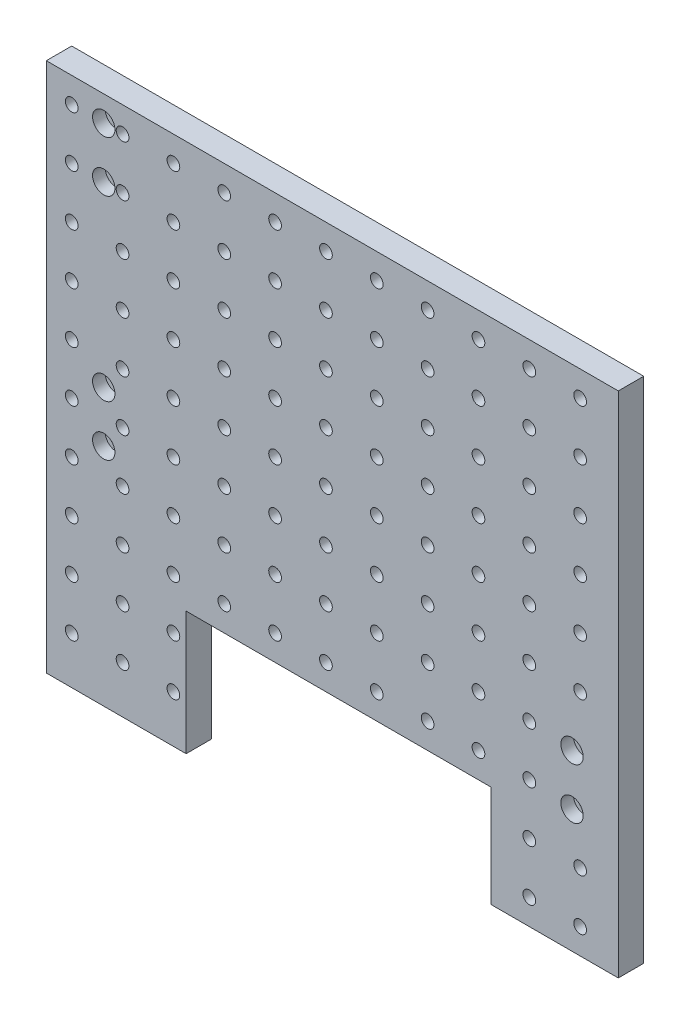
SolidWorks part; units mm, degrees
ref_plane "Front Plane" through (0, 0, 0) normal (0, 0, 1) x (1, 0, 0)
ref_plane "Top Plane" through (0, 0, 0) normal (0, 1, 0) x (1, 0, 0)
ref_plane "Right Plane" through (0, 0, 0) normal (1, 0, 0) x (0, 0, -1)
sketch "Sketch1" plane through (0, 0, 0) normal (0, 0, 1) x (1, 0, 0)
  line L1 (69.85, 0) -> (222.25, 0)
  line L2 (0, 0) -> (0, 203.2)
  line L3 (0, 203.2) -> (285.75, 203.2)
  line L4 (285.75, 0) -> (285.75, 203.2)
  line L6 (285.75, 0) -> (285.75, -50.8)
  line L7 (285.75, -50.8) -> (222.25, -50.8)
  line L8 (222.25, 0) -> (222.25, -50.8)
  line L10 (0, 0) -> (0, -61.722)
  line L11 (0, -61.722) -> (69.85, -61.722)
  line L12 (69.85, 0) -> (69.85, -61.722)
  circle A0 centre (12.7, 190.5) radius 3.175
  circle A1 centre (38.1, 190.5) radius 3.175
  circle A2 centre (63.5, 190.5) radius 3.175
  circle A3 centre (88.9, 190.5) radius 3.175
  circle A4 centre (114.3, 190.5) radius 3.175
  circle A5 centre (139.7, 190.5) radius 3.175
  circle A6 centre (165.1, 190.5) radius 3.175
  circle A7 centre (190.5, 190.5) radius 3.175
  circle A8 centre (215.9, 190.5) radius 3.175
  circle A9 centre (241.3, 190.5) radius 3.175
  circle A10 centre (266.7, 190.5) radius 3.175
  circle A11 centre (38.1, 165.1) radius 3.175
  circle A12 centre (63.5, 165.1) radius 3.175
  circle A13 centre (88.9, 165.1) radius 3.175
  circle A14 centre (114.3, 165.1) radius 3.175
  circle A15 centre (139.7, 165.1) radius 3.175
  circle A16 centre (165.1, 165.1) radius 3.175
  circle A17 centre (190.5, 165.1) radius 3.175
  circle A18 centre (215.9, 165.1) radius 3.175
  circle A19 centre (241.3, 165.1) radius 3.175
  circle A20 centre (266.7, 165.1) radius 3.175
  circle A21 centre (38.1, 139.7) radius 3.175
  circle A22 centre (63.5, 139.7) radius 3.175
  circle A23 centre (88.9, 139.7) radius 3.175
  circle A24 centre (114.3, 139.7) radius 3.175
  circle A25 centre (139.7, 139.7) radius 3.175
  circle A26 centre (165.1, 139.7) radius 3.175
  circle A27 centre (190.5, 139.7) radius 3.175
  circle A28 centre (215.9, 139.7) radius 3.175
  circle A29 centre (241.3, 139.7) radius 3.175
  circle A30 centre (266.7, 139.7) radius 3.175
  circle A31 centre (38.1, 114.3) radius 3.175
  circle A32 centre (63.5, 114.3) radius 3.175
  circle A33 centre (88.9, 114.3) radius 3.175
  circle A34 centre (114.3, 114.3) radius 3.175
  circle A35 centre (139.7, 114.3) radius 3.175
  circle A36 centre (165.1, 114.3) radius 3.175
  circle A37 centre (190.5, 114.3) radius 3.175
  circle A38 centre (215.9, 114.3) radius 3.175
  circle A39 centre (241.3, 114.3) radius 3.175
  circle A40 centre (266.7, 114.3) radius 3.175
  circle A41 centre (38.1, 88.9) radius 3.175
  circle A42 centre (63.5, 88.9) radius 3.175
  circle A43 centre (88.9, 88.9) radius 3.175
  circle A44 centre (114.3, 88.9) radius 3.175
  circle A45 centre (139.7, 88.9) radius 3.175
  circle A46 centre (165.1, 88.9) radius 3.175
  circle A47 centre (190.5, 88.9) radius 3.175
  circle A48 centre (215.9, 88.9) radius 3.175
  circle A49 centre (241.3, 88.9) radius 3.175
  circle A50 centre (266.7, 88.9) radius 3.175
  circle A51 centre (38.1, 63.5) radius 3.175
  circle A52 centre (63.5, 63.5) radius 3.175
  circle A53 centre (88.9, 63.5) radius 3.175
  circle A54 centre (114.3, 63.5) radius 3.175
  circle A55 centre (139.7, 63.5) radius 3.175
  circle A56 centre (165.1, 63.5) radius 3.175
  circle A57 centre (190.5, 63.5) radius 3.175
  circle A58 centre (215.9, 63.5) radius 3.175
  circle A59 centre (241.3, 63.5) radius 3.175
  circle A60 centre (266.7, 63.5) radius 3.175
  circle A61 centre (38.1, 38.1) radius 3.175
  circle A62 centre (63.5, 38.1) radius 3.175
  circle A63 centre (88.9, 38.1) radius 3.175
  circle A64 centre (114.3, 38.1) radius 3.175
  circle A65 centre (139.7, 38.1) radius 3.175
  circle A66 centre (165.1, 38.1) radius 3.175
  circle A67 centre (190.5, 38.1) radius 3.175
  circle A68 centre (215.9, 38.1) radius 3.175
  circle A69 centre (241.3, 38.1) radius 3.175
  circle A71 centre (38.1, 12.7) radius 3.175
  circle A72 centre (63.5, 12.7) radius 3.175
  circle A73 centre (88.9, 12.7) radius 3.175
  circle A74 centre (114.3, 12.7) radius 3.175
  circle A75 centre (139.7, 12.7) radius 3.175
  circle A76 centre (165.1, 12.7) radius 3.175
  circle A77 centre (190.5, 12.7) radius 3.175
  circle A78 centre (215.9, 12.7) radius 3.175
  circle A79 centre (241.3, 12.7) radius 3.175
  circle A81 centre (38.1, -12.7) radius 3.175
  circle A82 centre (63.5, -12.7) radius 3.175
  circle A89 centre (241.3, -12.7) radius 3.175
  circle A90 centre (266.7, -12.7) radius 3.175
  circle A91 centre (38.1, -38.1) radius 3.175
  circle A92 centre (63.5, -38.1) radius 3.175
  circle A99 centre (241.3, -38.1) radius 3.175
  circle A100 centre (266.7, -38.1) radius 3.175
  circle A101 centre (12.7, 165.1) radius 3.175
  circle A102 centre (12.7, 139.7) radius 3.175
  circle A103 centre (12.7, 114.3) radius 3.175
  circle A104 centre (12.7, 88.9) radius 3.175
  circle A105 centre (12.7, 63.5) radius 3.175
  circle A106 centre (12.7, 38.1) radius 3.175
  circle A107 centre (12.7, 12.7) radius 3.175
  circle A108 centre (12.7, -12.7) radius 3.175
  circle A109 centre (12.7, -38.1) radius 3.175
  circle A110 centre (88.9, -12.7) radius 3.175 [skipped]
  circle A111 centre (114.3, -12.7) radius 3.175 [skipped]
  circle A112 centre (139.7, -12.7) radius 3.175 [skipped]
  circle A113 centre (165.1, -12.7) radius 3.175 [skipped]
  circle A114 centre (190.5, -12.7) radius 3.175 [skipped]
  circle A115 centre (215.9, -12.7) radius 3.175 [skipped]
  circle A116 centre (215.9, -38.1) radius 3.175 [skipped]
  circle A117 centre (190.5, -38.1) radius 3.175 [skipped]
  circle A118 centre (165.1, -38.1) radius 3.175 [skipped]
  circle A119 centre (139.7, -38.1) radius 3.175 [skipped]
  circle A120 centre (114.3, -38.1) radius 3.175 [skipped]
  circle A121 centre (88.9, -38.1) radius 3.175 [skipped]
  circle A122 centre (266.7, 38.1) radius 3.175 [skipped]
  circle A123 centre (266.7, 12.7) radius 3.175 [skipped]
  dimension "D7" = 6.35
  dimension "D1" = 203.2
  dimension "D2" = 285.75
  dimension "D3" = 50.8
  dimension "D4" = 63.5
  dimension "D5" = 61.722
  dimension "D6" = 69.85
  dimension "D8" = 12.7
  dimension "D9" = 12.7
  dimension "D10" = 11
  dimension "D11" = 10
extrude "Boss-Extrude2" add sketch "Sketch1" along normal blind 12.7
sketch "Sketch2" plane through (0, 0, 12.7) normal (0, 0, 1) x (1, 0, 0)
  line L0 (285.75, 203.2) -> (0, 203.2) construction
  line L1 (0, 203.2) -> (0, -61.722) construction
  line L2 (222.25, -50.8) -> (285.75, -50.8) construction
  line L3 (285.75, -50.8) -> (285.75, 203.2) construction
  circle A0 centre (28.702, 76.2) radius 3.429
  circle A1 centre (28.702, 50.8) radius 3.429
  circle A2 centre (28.702, 76.2) radius 5.588
  circle A3 centre (28.702, 50.8) radius 5.588
  circle A4 centre (262.636, 10.668) radius 3.429
  circle A5 centre (262.636, 10.668) radius 5.588
  circle A6 centre (262.636, 36.068) radius 3.429
  circle A7 centre (262.636, 36.068) radius 5.588
  circle A8 centre (28.702, 165.1) radius 3.429
  circle A9 centre (28.702, 165.1) radius 5.588
  circle A10 centre (28.702, 190.5) radius 3.429
  circle A11 centre (28.702, 190.5) radius 5.588
  dimension "D2" = 6.858
  dimension "D3" = 6.858
  dimension "D4" = 11.176
  dimension "D7" = 6.858
  dimension "D8" = 11.176
  dimension "D12" = 6.858
  dimension "D13" = 11.176
  dimension "D1" = 25.4
  dimension "D5" = 127
  dimension "D6" = 28.702
  dimension "D9" = 25.4
  dimension "D10" = 61.468
  dimension "D11" = 23.114
  dimension "D14" = 25.4
  dimension "D15" = 88.9
extrude "Cut-Extrude1" cut sketch "Sketch2" against normal blind 12.7 contours A0 | A1
extrude "Cut-Extrude2" cut sketch "Sketch2<3>" against normal blind 6.35 contours A6 | A4 | A7 | A5 | A3 | A2
sketch "Sketch2<3>" plane through (0, 0, 12.7) normal (0, 0, 1) x (1, 0, 0) same geometry as "Sketch2"
extrude "Cut-Extrude6" cut sketch "Sketch2<6>" against normal blind 12.7 contours A6 | A4 region at (262.636, 10.668, 12.7) region at (262.636, 36.068, 12.7)
sketch "Sketch2<6>" plane through (0, 0, 12.7) normal (0, 0, 1) x (1, 0, 0) same geometry as "Sketch2"
extrude "Cut-Extrude7" cut sketch "Sketch2<7>" against normal blind 12.7 contours A10 | A8 region at (28.702, 165.1, 12.7) region at (28.702, 190.5, 12.7)
sketch "Sketch2<7>" plane through (0, 0, 12.7) normal (0, 0, 1) x (1, 0, 0) same geometry as "Sketch2"
extrude "Cut-Extrude8" cut sketch "Sketch2<8>" against normal blind 6.35 contours A9 A8 | A11 region at (23.2721, 165.1, 12.7)
sketch "Sketch2<8>" plane through (0, 0, 12.7) normal (0, 0, 1) x (1, 0, 0) same geometry as "Sketch2"
